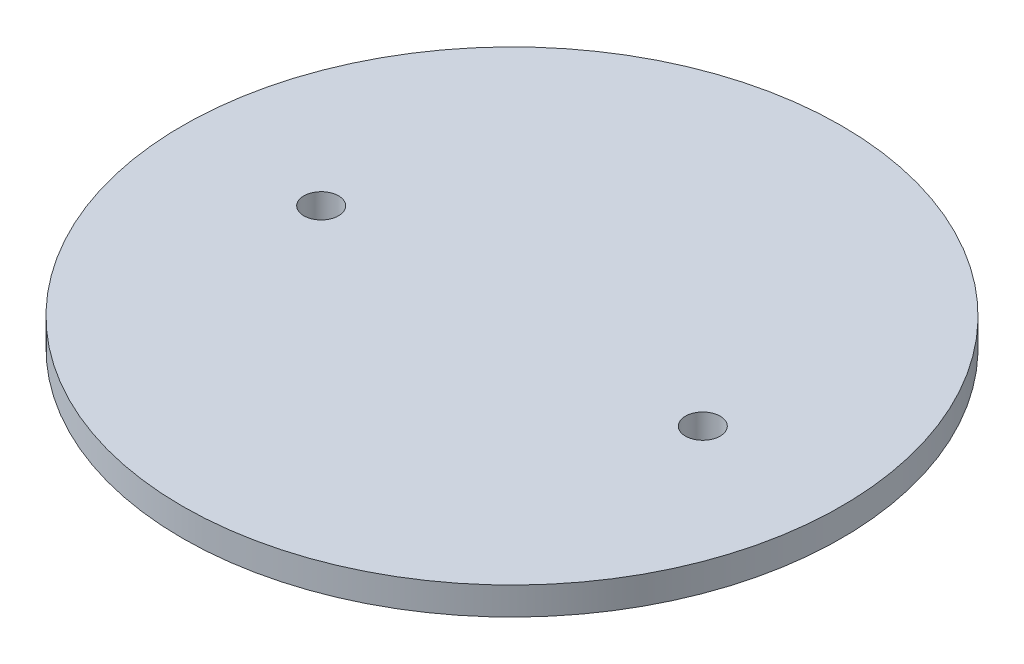
SolidWorks part; units mm, degrees
ref_plane "Front Plane" through (0, 0, 0) normal (0, 0, 1) x (1, 0, 0)
ref_plane "Top Plane" through (0, 0, 0) normal (0, 1, 0) x (1, 0, 0)
ref_plane "Right Plane" through (0, 0, 0) normal (1, 0, 0) x (0, 0, -1)
sketch "Sketch1" plane through (0, 0, 0) normal (0, 1, 0) x (1, 0, 0)
  circle A0 centre (0, 0) radius 47.5
  dimension "D1" = 95
extrude "Boss-Extrude1" add sketch "Sketch1" along normal blind 4
sketch "Sketch2" plane through (0, 4, 0) normal (0, 1, 0) x (1, 0, 0)
  line L0 (-47.5, 0) -> (47.5, 0) construction
  line L1 (0, 47.5) -> (0, -47.5) construction
  circle A0 centre (0, 0) radius 47.5 construction
  circle A1 centre (-27.5, 0) radius 2.5
  circle A2 centre (27.5, 0) radius 2.5
  point P9 (0, 0)
  dimension "D1" = 5
  dimension "D2" = 55
extrude "Cut-Extrude1" cut sketch "Sketch2" against normal through all
